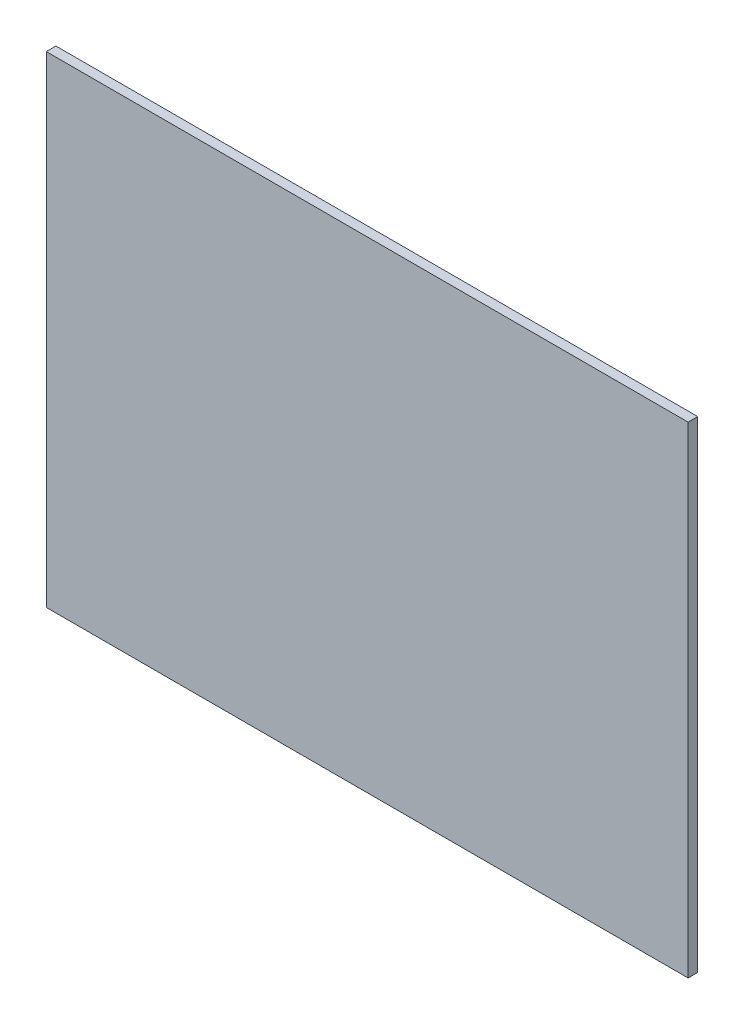
SolidWorks part; units mm, degrees
ref_plane "Front Plane" through (0, 0, 0) normal (0, 0, 1) x (1, 0, 0)
ref_plane "Top Plane" through (0, 0, 0) normal (0, 1, 0) x (1, 0, 0)
ref_plane "Right Plane" through (0, 0, 0) normal (1, 0, 0) x (0, 0, -1)
sketch "Sketch1" plane through (0, 0, 0) normal (0, 0, 1) x (1, 0, 0)
  line L1 (-100, 75) -> (100, 75)
  line L2 (-100, 75) -> (-100, -75)
  line L3 (-100, -75) -> (100, -75)
  line L4 (100, 75) -> (100, -75)
  line L5 (-100, 75) -> (100, -75) construction
  line L6 (-100, -75) -> (100, 75) construction
  point P0 (0, 0)
  dimension "D1" = 150
  dimension "D2" = 200
extrude "Boss-Extrude1" add sketch "Sketch1" along normal blind 3
